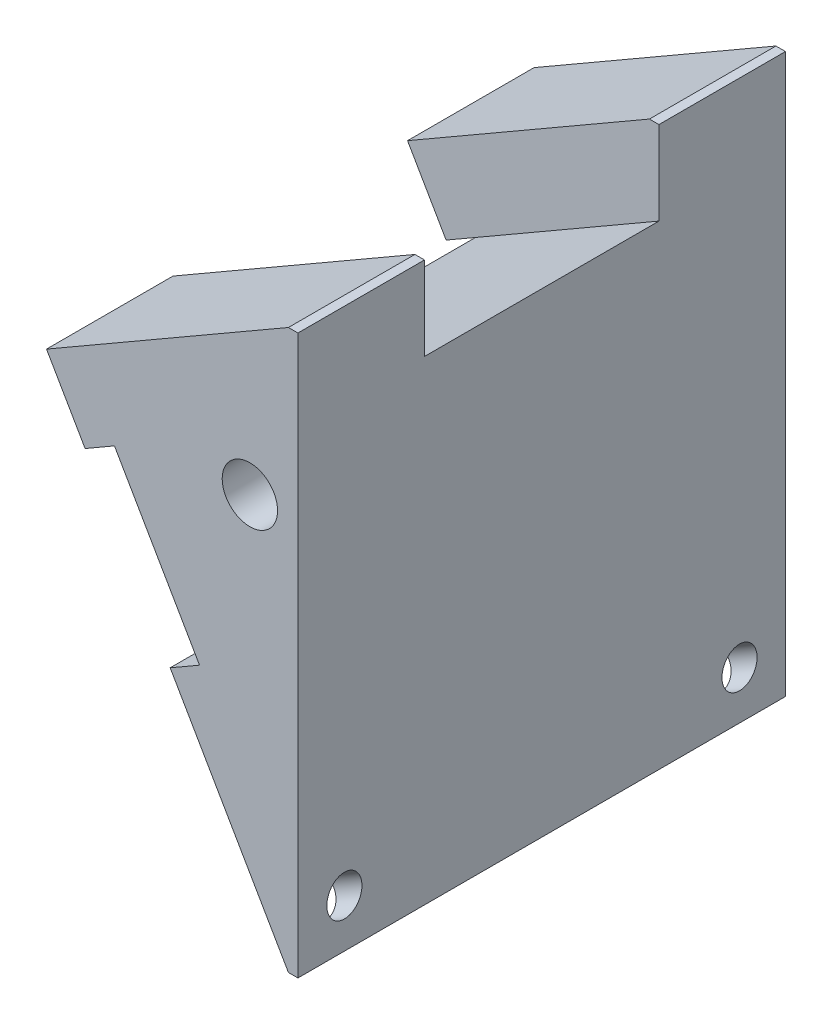
SolidWorks part; units mm, degrees
ref_plane "Front Plane" through (0, 0, 0) normal (0, 0, 1) x (1, 0, 0)
ref_plane "Top Plane" through (0, 0, 0) normal (0, 1, 0) x (1, 0, 0)
ref_plane "Right Plane" through (0, 0, 0) normal (1, 0, 0) x (0, 0, -1)
sketch "Sketch1" plane through (0, 0, 0) normal (0, 1, 0) x (1, 0, 0)
  line L1 (-3.2379, 12.1432) -> (2.9782, 12.1432)
  line L2 (-3.2379, 12.1432) -> (-3.2379, -15.2618)
  line L3 (-3.2379, -15.2618) -> (2.9782, -15.2618)
  line L4 (2.9782, 12.1432) -> (2.9782, -15.2618)
  line L5 (9.0361, -15.5158) -> (3.8301, -15.5158) construction
  line L7 (9.0361, 12.3972) -> (3.8301, 12.3972) construction
  dimension "D1" = 0.254
  dimension "D2" = 0.254
extrude "Boss-Extrude1" add sketch "Sketch1" against normal up to vertex (18.1251 mm away) and the other way blind 11.938
ref_plane "Plane1" through (0, 0, -12.1432) normal (0, 0, -1) x (-1, 0, 0)
sketch "Sketch2" plane through (0, 0, -12.1432) normal (0, 0, -1) x (-1, 0, 0)
  line L0 (15.3378, 5.1421) -> (3.2379, 12.128)
  line L2 (-2.9782, 11.938) -> (-2.9782, 12.128)
  line L3 (-2.9782, 12.128) -> (3.2379, 12.128)
  line L4 (-2.9782, 11.938) -> (3.2379, 11.938)
  line L5 (3.2379, 11.938) -> (3.2379, -18.1251)
  line L6 (3.2379, -18.1251) -> (9.6408, -7.035)
  line L11 (15.0679, 2.3651) -> (16.3379, 4.5648)
  line L12 (16.3379, 4.5648) -> (15.3378, 5.1421)
  line L13 (15.0679, 2.3651) -> (14.248, 0.945)
  line L14 (3.2379, -18.1251) -> (16.3379, 4.5648) construction
  line L16 (8.1977, -5.8621) -> (12.6578, 1.8631)
  line L17 (12.6578, 1.8631) -> (14.248, 0.945)
  line L18 (8.1977, -5.8621) -> (8.0506, -6.1169)
  line L19 (8.0506, -6.1169) -> (9.6408, -7.035)
extrude "Boss-Extrude2" add sketch "Sketch2" against normal up to vertex (27.405 mm away)
sketch "Sketch3" plane through (-6.0611, 10.4981, 0) normal (-0.5, 0.866, 0) x (0.866, 0.5, 0)
  line L0 (-11.8666, -1.5593) -> (-11.8666, -7.9093)
  line L1 (-11.8666, -15.2618) -> (-11.8666, 12.1432) construction
  line L2 (-11.8666, -1.5593) -> (-11.8666, 4.7907)
  line L3 (-11.8666, 4.7907) -> (3.2599, 4.7907)
  line L4 (3.2599, -15.2618) -> (3.2599, 12.1432) construction
  line L6 (3.2599, -7.9093) -> (-11.8666, -7.9093)
  line L7 (3.2599, 4.7907) -> (8.6432, 4.7907)
  line L8 (8.6432, -15.2618) -> (8.6432, 12.1432) construction
  line L9 (8.6432, 4.7907) -> (8.6432, -7.9093)
  line L10 (8.6432, -7.9093) -> (3.2599, -7.9093)
  dimension "D1" = 6.35
  dimension "D2" = 6.35
extrude "Cut-Extrude1" cut sketch "Sketch3" against normal up to vertex (4.1797 mm away) up to point (-14.248, 0.945, 15.2618)
ref_plane "Plane2" through (-10.2768, -5.9333, 0) normal (-0.866, -0.5, 0) x (0, 0, 1)
sketch "Sketch4" plane through (-10.2768, -5.9333, 0) normal (-0.866, -0.5, 0) x (0, 0, 1)
  circle A1 centre (12.2458, 10.1221) radius 0.95
  circle A2 centre (-9.1542, 10.1221) radius 0.95
  circle A3 centre (-9.1542, -12.0779) radius 0.95
  circle A4 centre (12.2458, -12.0779) radius 0.95
  dimension "D1" = 1.9
  dimension "D2" = 1.9
  dimension "D3" = 1.9
  dimension "D4" = 1.9
extrude "Cut-Extrude2" cut sketch "Sketch4" against normal blind 6.604
sketch "Sketch7" plane through (0, 0, -12.1432) normal (0, 0, -1) x (-1, 0, 0)
  line L0 (-2.9782, -18.1251) -> (3.2379, -18.1251) construction
  line L1 (-2.9782, 12.128) -> (2.7212, 12.128)
  line L2 (-2.9782, 12.128) -> (-2.9782, -18.1251)
  line L3 (-2.9782, -18.1251) -> (2.7212, -18.1251)
  line L4 (2.7212, 12.128) -> (2.7212, -18.1251)
  line L5 (2.7212, -18.9365) -> (2.7212, 23.4563) construction
extrude "Cut-Extrude3" cut sketch "Sketch7" against normal blind 31.242
sketch "Sketch8" plane through (0, 0, -12.1432) normal (0, 0, -1) x (-1, 0, 0)
  line L0 (6.8242, 3.2412) -> (3.8242, 3.2412) construction
  line L1 (6.8242, -5.7753) -> (6.8242, 20.0239) construction
  line L2 (3.8242, 20.0239) -> (3.8242, -5.7753) construction
  circle A0 centre (5.3242, 3.2412) radius 1.5
  dimension "D1" = 3
extrude "Cut-Extrude4" cut sketch "Sketch8" against normal blind 32.004
sketch "Sketch9" plane through (-10.2768, -5.9333, 0) normal (-0.866, -0.5, 0) x (0, 0, 1)
  line L6 (-12.1432, 11.0106) -> (-12.1432, -11.0106) construction
  line L7 (-12.1432, 12.1221) -> (-11.6432, 12.1221)
  line L8 (-12.1432, 12.1221) -> (-12.1432, -14.3362)
  line L9 (-12.1432, -14.3362) -> (-11.6432, -14.3362)
  line L10 (-11.6432, 12.1221) -> (-11.6432, -14.3362)
  line L11 (-4.7907, 12.1221) -> (-12.1432, 12.1221) construction
  line L12 (15.2618, -14.3362) -> (-12.1432, -14.3362) construction
  line L13 (1.5593, -14.3362) -> (1.5593, 12.1221) construction
  line L14 (14.7618, 12.1221) -> (14.7618, -14.3362)
  line L15 (15.2618, -14.3362) -> (14.7618, -14.3362)
  line L16 (15.2618, 12.1221) -> (15.2618, -14.3362)
  line L17 (15.2618, 12.1221) -> (14.7618, 12.1221)
  dimension "D1" = 0.5
extrude "Cut-Extrude5" cut sketch "Sketch9" against normal blind 20
sketch "Sketch10" plane through (-3.9712, 6.8784, 0) normal (-0.5, 0.866, 0) x (0.866, 0.5, 0)
  line L0 (1.4434, -1.5593) -> (-1.3936, -1.5593) construction
  line L1 (1.4434, -7.9093) -> (1.4434, 4.7907) construction
